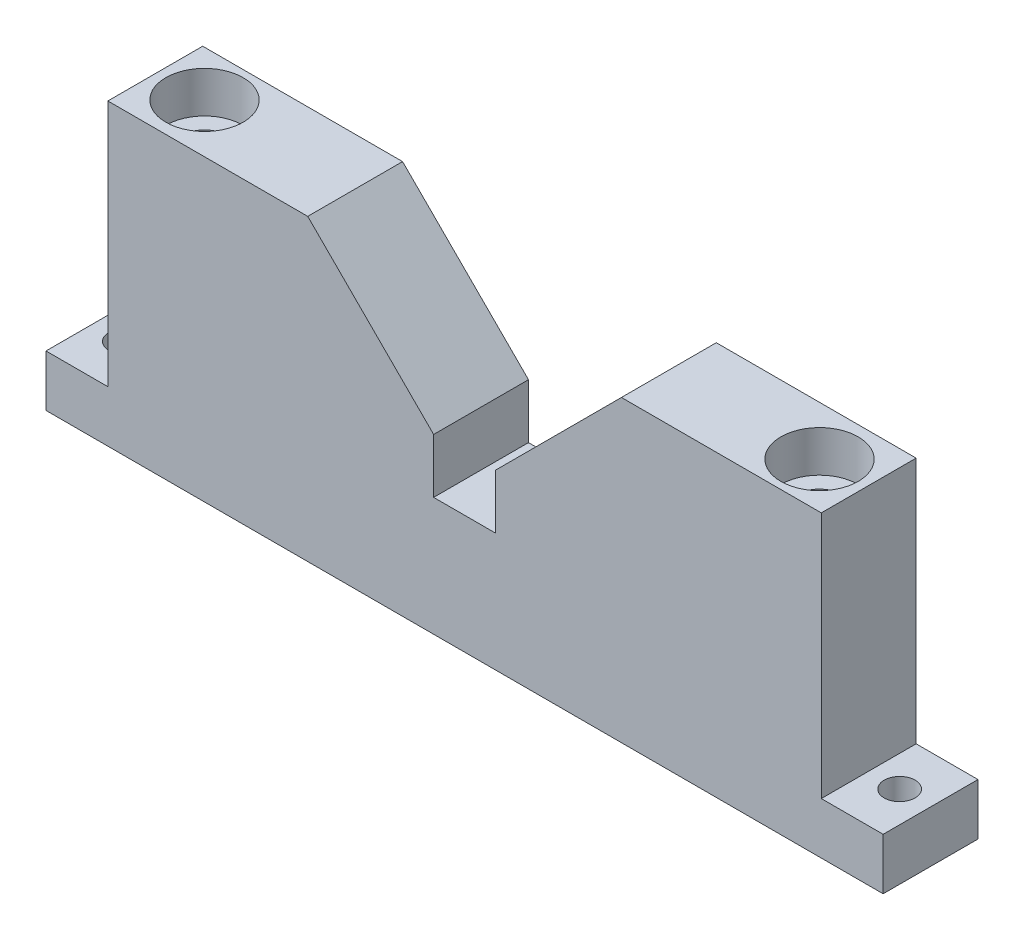
SolidWorks part; units mm, degrees
ref_plane "Спереди" through (0, 0, 0) normal (0, 0, 1) x (1, 0, 0)
ref_plane "Сверху" through (0, 0, 0) normal (0, 1, 0) x (1, 0, 0)
ref_plane "Справа" through (0, 0, 0) normal (1, 0, 0) x (0, 0, -1)
sketch "Эскиз1" plane through (0, 0, 0) normal (0, 0, 1) x (1, 0, 0)
  line L0 (-69.2, -12) -> (-30.4264, -12)
  line L1 (-30.4264, -12) -> (-6, -36.4264)
  line L2 (-6, -36.4264) -> (-6, -47)
  line L3 (-6, -47) -> (6, -47)
  line L4 (6, -47) -> (6, -36.4264)
  line L5 (6, -36.4264) -> (30.4264, -12)
  line L6 (30.4264, -12) -> (69.2, -12)
  line L7 (69.2, -12) -> (69.2, -60)
  line L8 (69.2, -60) -> (-69.2, -60)
  line L9 (-69.2, -60) -> (-69.2, -12)
  circle A0 centre (0, 0) radius 30 construction
  dimension "D1" = 60
  dimension "D3" = 60
  dimension "D2" = 12
  dimension "D4" = 138.4
  dimension "D5" = 12
  dimension "D6" = 35
extrude "Бобышка-Вытянуть1" add sketch "Эскиз1" along normal mid plane 18.4
sketch "Эскиз2" plane through (0, -60, 0) normal (0, -1, 0) x (1, 0, 0)
  line L0 (-81.2, -9.2) -> (81.2, 9.2) construction
  line L1 (-81.2, 9.2) -> (81.2, 9.2)
  line L2 (-81.2, 9.2) -> (-81.2, -9.2)
  line L3 (-81.2, -9.2) -> (81.2, -9.2)
  line L4 (81.2, 9.2) -> (81.2, -9.2)
  line L6 (-69.2, 9.2) -> (69.2, 9.2) construction
  dimension "D1" = 162.4
extrude "Бобышка-Вытянуть2" add sketch "Эскиз2" along normal blind 10
hole_wizard "Цековка для винта с внутренним шестигранником M82" positions "Эскиз12" profile "Эскиз11" counterbore size "M8" standard "ISO" end condition through all
sketch "Эскиз12" plane through (0, -12, 0) normal (0, 1, 0) x (-1, 0, 0)
  line L0 (60, -0.3438) -> (-60, 0.3438) construction
  point P0 (-60, 0.3438)
  point P1 (60, -0.3438)
  dimension "D1" = 120
sketch "Эскиз11" plane through (60, -12, 0.3438) normal (1, 0, 0) x (0, 0, 1)
  line L0 (0, 0) -> (0, 58)
  line L1 (0, 58) -> (4.2, 58)
  line L3 (4.2, 58) -> (4.2, 8)
  line L4 (4.2, 8) -> (7.5, 8)
  line L5 (7.5, 8) -> (7.5, 0)
  line L7 (7.5, 0) -> (0, 0)
  line L11 (0, -6.35) -> (0, 107.95) construction
  dimension "Диаметр сквозного отверстия" = 8.4
  dimension "Глубина сквозного отверстия" = 58
  dimension "Диаметр цековки" = 15
  dimension "Глубина цековки" = 8
hole_wizard "Диаметр отверстия Ø6.0 (6)2" positions "Эскиз14" profile "Эскиз13" hole size "Ø6.0" standard "ISO" end condition through all
sketch "Эскиз14" plane through (0, -60, 0) normal (0, 1, 0) x (-1, 0, 0)
  line L0 (-75.2, 0) -> (75.2, 0) construction
  line L3 (-81.2, -9.2) -> (-81.2, 9.2) construction
  point P0 (-75.2, 0)
  point P1 (75.2, 0)
  dimension "D1" = 6
sketch "Эскиз13" plane through (75.2, -60, 0) normal (1, 0, 0) x (0, 0, 1)
  line L0 (0, 0) -> (0, 10)
  line L1 (0, 10) -> (3, 10)
  line L2 (3, 10) -> (3, 0)
  line L5 (3, 0) -> (0, 0)
  line L11 (0, -6.35) -> (0, 107.95) construction
  dimension "Диаметр сквозного отверстия" = 6
  dimension "Глубина сквозного отверстия" = 10
ref_plane "mount-plane-1" through (-21.2132, -21.2132, 0) normal (0.7071, 0.7071, 0) x (0.7071, -0.7071, 0)
ref_plane "mount-plane-2" through (21.2132, -21.2132, 0) normal (-0.7071, 0.7071, 0) x (0, 0, 1)
equation "\"D\"= 60"
equation "\"D1@Эскиз1\" = \"D\""
equation "\"D2@Эскиз1\" = \"D\"/5"
equation "\"D3@Эскиз1\" = \"D\""
equation "\"D4@Эскиз1\" = 2*\"D\"+\"Диаметр сквозного отверстия@Эскиз11\"+10"
equation "\"D1@Бобышка-Вытянуть1\" = \"Диаметр сквозного отверстия@Эскиз11\"+10"
equation "\"D1@Эскиз12\" = \"D4@Эскиз1\"- \"Диаметр сквозного отверстия@Эскиз11\"-10"
equation "\"D5@Эскиз1\" = \"D1@Эскиз1\"/5"
equation "\"D6@Эскиз1\" = \"D1@Эскиз1\"/2+5"
equation "\"D1@Эскиз2\" = \"D4@Эскиз1\"+\"Диаметр сквозного отверстия@Эскиз13\"*4"
equation "\"D1@Эскиз14\" = \"Диаметр сквозного отверстия@Эскиз13\""
